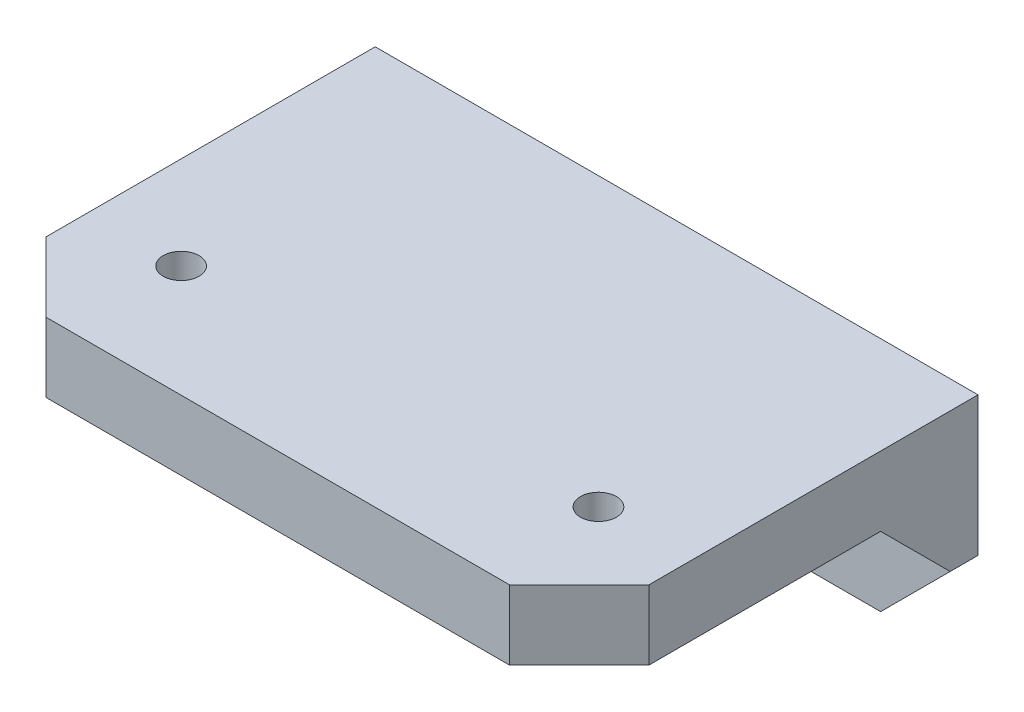
SolidWorks part; units mm, degrees
material "PET"
ref_plane "Front Plane" through (0, 0, 0) normal (0, 0, 1) x (1, 0, 0)
ref_plane "Top Plane" through (0, 0, 0) normal (0, 1, 0) x (1, 0, 0)
ref_plane "Right Plane" through (0, 0, 0) normal (1, 0, 0) x (0, 0, -1)
sketch "Sketch1" plane through (0, 0, 0) normal (0, 0, 1) x (1, 0, 0)
  line L1 (-151.095, -53.975) -> (-126.4888, -53.975)
  line L2 (-209.0388, -25.4) -> (-126.4888, -25.4)
  line L3 (-209.0388, -25.4) -> (-209.0388, -53.975)
  line L4 (-209.0388, -53.975) -> (-151.095, -53.975)
  line L5 (-126.4888, -25.4) -> (-126.4888, -53.975)
extrude "Boss-Extrude1" add sketch "Sketch1" along normal blind 6.35
sketch "Sketch2" plane through (0, 0, 6.35) normal (0, 0, 1) x (1, 0, 0)
  line L0 (-126.4888, -53.975) -> (-126.4888, -25.4) construction
  line L1 (-209.0388, -25.4) -> (-126.4888, -25.4)
  line L2 (-209.0388, -25.4) -> (-209.0388, -34.925)
  line L3 (-209.0388, -34.925) -> (-126.4888, -34.925)
  line L4 (-126.4888, -25.4) -> (-126.4888, -34.925)
  dimension "D1" = 9.525
extrude "Boss-Extrude2" add sketch "Sketch2" along normal blind 50.8
chamfer "Chamfer1" distance 9.525 angle 45 5 edges at (-167.7638, -34.925, 6.35) (-126.4888, -53.975, 3.175) (-126.4888, -30.1625, 57.15) (-209.0388, -30.1625, 57.15) (-209.0388, -53.975, 3.175)
hole_wizard "#8 Clearance Hole1" positions "Sketch3" profile "Sketch4" hole size "#8" standard "ANSI Inch" end condition through all
sketch "Sketch3" plane through (0, 0, 57.15) normal (0, 0, 1) x (1, 0, 0)
  line L0 (-126.4888, -44.45) -> (-209.0388, -44.45) construction
  line L1 (-209.0388, -44.45) -> (-209.0388, -34.925) construction
  line L2 (-126.4888, -34.925) -> (-126.4888, -44.45) construction
  point P0 (-193.1638, -44.45)
  point P2 (-142.3638, -44.45)
  dimension "D1" = 15.875
  dimension "D2" = 15.875
sketch "Sketch4" plane through (-193.1638, -44.45, 57.15) normal (1, 0, 0) x (0, -1, 0)
  line L0 (0, 0) -> (0, 57.15)
  line L1 (0, 57.15) -> (2.4574, 57.15)
  line L2 (2.4574, 57.15) -> (2.4574, 0)
  line L5 (2.4574, 0) -> (0, 0)
  line L11 (0, -6.35) -> (0, 107.95) construction
  dimension "Thru Hole Dia." = 4.9149
  dimension "Thru Hole Depth" = 57.15
sketch "Sketch5" plane through (0, 0, 6.35) normal (0, 0, 1) x (1, 0, 0)
  circle A0 centre (-193.1638, -44.45) radius 6.35
  circle A1 centre (-142.3638, -44.45) radius 6.35
  dimension "D1" = 12.7
extrude "Cut-Extrude1" cut sketch "Sketch5" along normal up to next
hole_wizard "#8 Clearance Hole2" positions "Sketch6" profile "Sketch7" hole size "#8" standard "ANSI Inch" end condition through all
sketch "Sketch6" plane through (0, -34.925, 0) normal (0, -1, 0) x (-1, 0, 0)
  line L0 (209.0388, -47.625) -> (209.0388, -15.875) construction
  line L1 (126.4888, -47.625) -> (126.4888, -15.875) construction
  point P0 (196.3388, -41.8183)
  point P2 (139.1888, -41.8183)
  dimension "D1" = 12.7
  dimension "D2" = 12.7
sketch "Sketch7" plane through (-196.3388, -34.925, 41.8183) normal (1, 0, 0) x (0, 0, -1)
  line L0 (0, 0) -> (0, 9.525)
  line L1 (0, 9.525) -> (2.4574, 9.525)
  line L2 (2.4574, 9.525) -> (2.4574, 0)
  line L5 (2.4574, 0) -> (0, 0)
  line L11 (0, -6.35) -> (0, 107.95) construction
  dimension "Thru Hole Dia." = 4.9149
  dimension "Thru Hole Depth" = 9.525
chamfer "Chamfer2" distance 2.54 angle 45 6 edges at (-167.7638, -25.4, 0) (-126.4888, -34.925, 0) (-131.2513, -49.2125, 0) (-167.7638, -53.975, 0) (-204.2763, -49.2125, 0) (-209.0388, -34.925, 0)
ref_plane "Plane4" through (-167.7638, 0, 0) normal (1, 0, 0) x (0, 0, -1)
